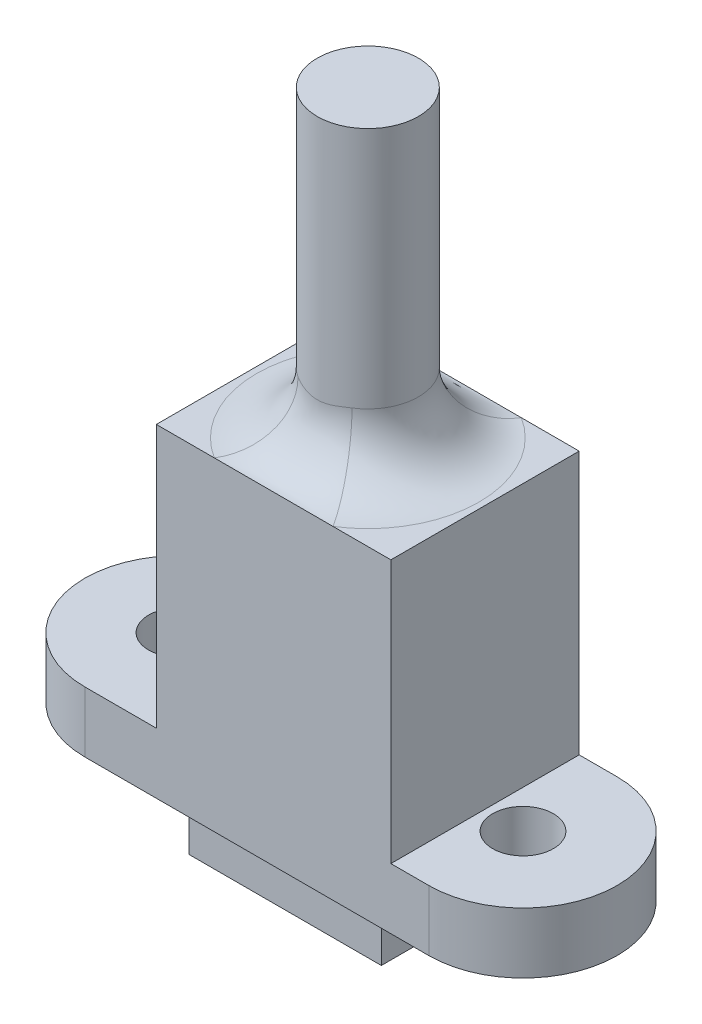
SolidWorks part; units mm, degrees
ref_plane "前视基准面" through (0, 0, 0) normal (0, 0, 1) x (1, 0, 0)
ref_plane "上视基准面" through (0, 0, 0) normal (0, 1, 0) x (1, 0, 0)
ref_plane "右视基准面" through (0, 0, 0) normal (1, 0, 0) x (0, 0, -1)
sketch "草图1" plane through (0, 0, 0) normal (0, 1, 0) x (1, 0, 0)
  line L0 (-9.3314, 0) -> (7.6686, 0) construction
  line L1 (-9.3314, 4.653) -> (7.6686, 4.653)
  line L2 (-9.3314, -4.653) -> (7.6686, -4.653)
  line L4 (-5.5814, 3.25) -> (3.9186, 3.25)
  line L5 (-5.5814, 3.25) -> (-5.5814, -3.25)
  line L6 (-5.5814, -3.25) -> (3.9186, -3.25)
  line L7 (3.9186, 3.25) -> (3.9186, -3.25)
  arc A0 (-9.3314, 4.653) -> (-9.3314, -4.653) centre (-9.3314, 0) ccw
  arc A1 (7.6686, -4.653) -> (7.6686, 4.653) centre (7.6686, 0) ccw
  circle A2 centre (-9.3314, 0) radius 1.5
  circle A3 centre (7.6686, 0) radius 1.5
  point P3 (-0.8314, 0)
  point P16 (-5.5814, 0)
  point P17 (-0.8314, -3.25)
  point P18 (-0.8314, -4.653)
  dimension "D2" = 3
  dimension "D3" = 3
  dimension "D1" = 17
  dimension "D4" = 9.5
  dimension "D5" = 6.5
extrude "凸台-拉伸1" add sketch "草图1" along normal blind 3 contours A1 L1 A0 L2
extrude "凸台-拉伸2" add sketch "草图1<3>" against normal blind 3 contours L5 L0 L7 L4 | L0 L5 L6 L7 region at (-0.8314, 0, -1.625) region at (-0.8314, 0, 1.625)
sketch "草图1<3>" plane through (0, 0, 0) normal (0, 1, 0) x (1, 0, 0) same geometry as "草图1"
extrude "切除-拉伸1" cut sketch "草图1<4>" along normal blind 3 contours A2 | A3 region at (-9.3314, 0, 0) region at (7.6686, 0, 0)
sketch "草图1<4>" plane through (0, 0, 0) normal (0, 1, 0) x (1, 0, 0) same geometry as "草图1"
sketch "草图2" plane through (0, -3, 0) normal (0, -1, 0) x (1, 0, 0)
  line L0 (-4.5814, 1.75) -> (2.9186, 1.75)
  line L1 (2.9186, 1.75) -> (2.3014, -1.75)
  line L2 (2.3014, -1.75) -> (-3.9643, -1.75)
  line L3 (-3.9643, -1.75) -> (-4.5814, 1.75)
  line L4 (-5.5814, 3.25) -> (3.9186, 3.25) construction
  line L5 (3.9186, -3.25) -> (3.9186, 3.25) construction
  point P4 (-0.8314, 1.75)
  point P7 (-0.8314, 3.25)
  point P8 (-4.2729, 0)
  point P11 (3.9186, 0)
  point P12 (-3.7228, 1.3625)
  dimension "D1" = 100
  dimension "D2" = 100
  dimension "D3" = 3.5
  dimension "D4" = 7.5
extrude "切除-拉伸2" cut sketch "草图2" against normal blind 3
sketch "草图3" plane through (0, 3, 0) normal (0, 1, 0) x (1, 0, 0)
  line L0 (-9.3314, 4.653) -> (7.6686, 4.653) construction
  line L1 (5.7921, 4.653) -> (-5.7983, 4.653)
  line L2 (5.7921, 4.653) -> (5.7921, -4.653)
  line L3 (5.7921, -4.653) -> (-5.7983, -4.653)
  line L4 (-5.7983, 4.653) -> (-5.7983, -4.653)
  line L5 (-9.3314, -4.653) -> (7.6686, -4.653) construction
extrude "凸台-拉伸3" add sketch "草图3" along normal blind 13
sketch "草图4" plane through (0, 16, 0) normal (0, 1, 0) x (1, 0, 0)
  circle A0 centre (0, 0) radius 2.5
  dimension "D1" = 5
extrude "凸台-拉伸4" add sketch "草图4" along normal blind 15
fillet "圆角1" radius 3 1 edges at (0, 16, 2.5)
